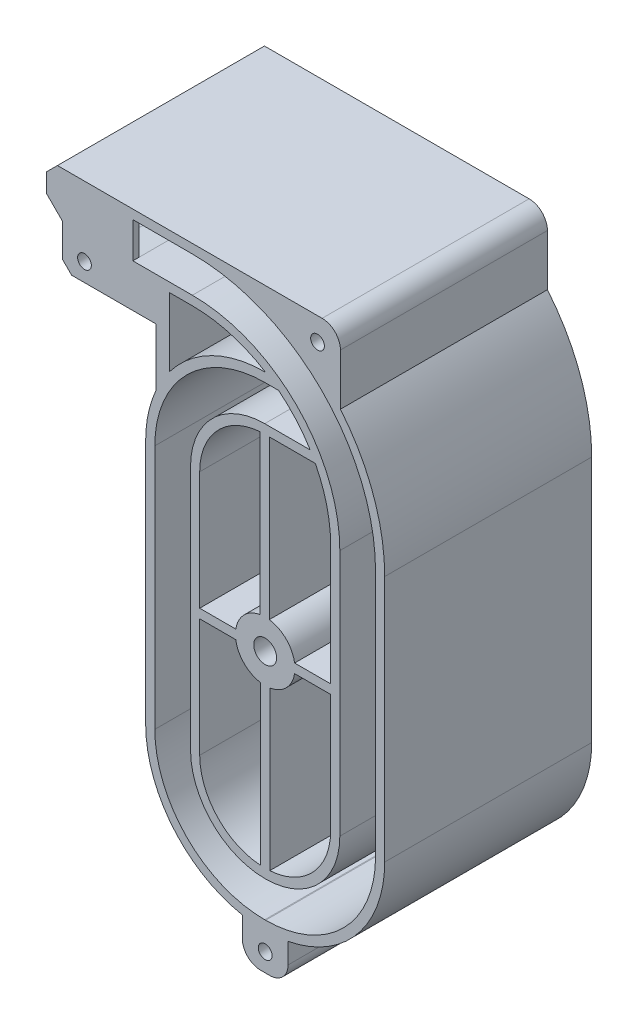
SolidWorks part; units mm, degrees
ref_plane "Front Plane" through (0, 0, 0) normal (0, 0, 1) x (1, 0, 0)
ref_plane "Top Plane" through (0, 0, 0) normal (0, 1, 0) x (1, 0, 0)
ref_plane "Right Plane" through (0, 0, 0) normal (1, 0, 0) x (0, 0, -1)
sketch "Sketch5" plane through (0, 0, 0) normal (0, 0, 1) x (1, 0, 0)
  line L5 (0, 0) -> (0, 6) construction
  line L6 (4.8529, 0) -> (10.55, 5.6971)
  line L11 (6.55, 0) -> (10.55, 4)
  line L18 (-2.55, 6) -> (-6.55, 2)
  line L19 (-6.55, 2) -> (-6.55, 0)
  line L20 (7.0145, 15.5645) -> (16.104, 18) construction
  line L23 (6.55, 0) -> (-6.55, 0)
  line L24 (-5.35, 1.5029) -> (-0.8529, 6)
  line L25 (-5.35, 1.5029) -> (-5.35, 0)
  line L26 (-2.55, 6) -> (-0.8529, 6) construction
  line L27 (-2.55, 6) -> (7.0145, 15.5645)
  line L28 (-0.8529, 6) -> (7.0145, 13.8674)
  line L29 (16.104, 16) -> (6.6006, 13.4536)
  line L31 (7.0145, 11.55) -> (7.0145, 15.5645)
  line L32 (16.104, 7) -> (16.104, 5.8) construction
  line L33 (16.104, 5.8) -> (16.104, 5) construction
  line L34 (7.0145, 13.8674) -> (6.6006, 13.4536)
  line L35 (10.55, 5.6971) -> (16.104, 7)
  line L36 (16.104, 7) -> (19.104, 7)
  line L38 (10.55, 4) -> (16.104, 5)
  line L41 (69.1095, -24) -> (69.1095, -78)
  line L42 (78.9095, -24) -> (78.9095, -78)
  line L44 (80.9095, -78) -> (80.9095, -24)
  line L46 (16.104, 16) -> (16.104, 18) construction
  line L49 (30.7095, -78) -> (30.7095, -24.3867)
  line L50 (71.1095, -24) -> (71.1095, -78)
  line L51 (19.104, 7) -> (19.104, 5.8) construction
  line L62 (16.104, 5) -> (19.104, 5)
  line L63 (19.104, 5) -> (19.104, 5.8) construction
  line L64 (19.104, 7) -> (25.9095, 8.2)
  line L73 (19.104, 5) -> (25.9095, 6.2)
  line L74 (16.104, 5.8) -> (19.104, 5.8) construction
  line L93 (63.9212, 18) -> (16.104, 18) construction
  line L94 (16.104, 16) -> (38.9095, 16)
  line L95 (6.8145, 15.3645) -> (6.8145, 11.4672) construction
  line L96 (25.9095, 8.2) -> (38.9095, 8.2)
  line L97 (7.0145, 15.5645) -> (9.45, 18)
  line L104 (6.8145, 11.4672) -> (10.35, 7.9316) construction
  line L105 (-6.55, 0) -> (-6.55, -1.2)
  line L106 (-6.55, -1.2) -> (6.55, -1.2)
  line L107 (6.55, -1.2) -> (6.55, 0)
  line L108 (-5.35, 0) -> (-5.35, -1.2)
  line L109 (4.8529, 0) -> (4.8529, -1.2)
  line L111 (10.55, 8.0145) -> (7.0145, 11.55)
  line L113 (10.35, 7.9316) -> (10.35, 3.8) construction
  line L114 (10.55, 4) -> (10.55, 8.0145)
  line L133 (9.45, 18) -> (38.9095, 18)
  line L134 (25.9095, 6.2) -> (38.9095, 6.2)
  line L135 (54.9095, -78) -> (80.9095, -78) construction
  line L137 (54.9095, -78) -> (54.9095, -104) construction
  line L138 (54.7095, -78) -> (54.7095, -104) construction
  line L139 (54.7095, -78) -> (28.7095, -78) construction
  line L140 (54.9095, -104) -> (54.7095, -104)
  line L141 (54.9095, -102) -> (54.7095, -102)
  line L142 (54.9095, -94.2) -> (54.7095, -94.2)
  line L143 (54.9095, -92.2) -> (54.7095, -92.2)
  line L146 (28.7095, -24.3867) -> (28.7095, -78)
  line L147 (40.5095, -24.3867) -> (40.5095, -78)
  line L148 (38.5095, -24.3867) -> (38.5095, -78)
  line L151 (54.7095, -24.3867) -> (28.7095, -24.3867) construction
  line L152 (54.7095, -24.3867) -> (54.7095, 1.6133) construction
  line L153 (54.7095, -24.3867) -> (69.1095, -24.3867) construction
  line L154 (54.7095, 1.6133) -> (54.9095, 1.6133)
  line L155 (54.7095, -0.3867) -> (57.7365, -0.3867)
  line L156 (54.7095, -8.1867) -> (66.9591, -8.1867)
  line L157 (54.7095, -10.1867) -> (67.9962, -10.1867)
  line L158 (69.1095, -51.1934) -> (40.5095, -51.1934) construction
  line L161 (48.3869, -50.1934) -> (40.5095, -50.1934)
  line L162 (61.2322, -50.1934) -> (69.1095, -50.1934)
  line L163 (48.3869, -52.1934) -> (40.5095, -52.1934)
  line L164 (61.2322, -52.1934) -> (69.1095, -52.1934)
  line L165 (30.9625, -13.8) -> (30.9625, 6.2)
  line L166 (33.9625, -8.7163) -> (33.9625, 6.2)
  line L167 (53.7095, -10.222) -> (53.7095, -44.7871)
  line L168 (68.1095, -78) -> (69.1095, -77)
  line L169 (54.9095, -91.2) -> (53.9095, -92.2)
  line L170 (55.7095, -10.222) -> (55.7095, -44.7871)
  line L171 (55.7095, -10.222) -> (55.7095, -10.1867)
  line L172 (53.8095, -57.616) -> (53.8095, -92.1715)
  line L173 (55.8095, -57.616) -> (55.8095, -92.1715)
  line L174 (7.0145, 14.1645) -> (16.104, 16)
  line L175 (10.55, 5.0971) -> (16.104, 7)
  line L176 (7.0145, 14.1645) -> (7.0145, 13.5645)
  arc A2 (80.9095, -24) -> (38.9095, 18) centre (38.9095, -24) ccw
  arc A9 (78.9095, -24) -> (38.9095, 16) centre (38.9095, -24) ccw
  arc A10 (71.1095, -24) -> (38.9095, 8.2) centre (38.9095, -24) ccw
  arc A11 (69.1095, -24) -> (38.9095, 6.2) centre (38.9095, -24) ccw
  arc A12 (54.9095, -102) -> (78.9095, -78) centre (54.9095, -78) ccw
  arc A13 (54.9095, -104) -> (80.9095, -78) centre (54.9095, -78) ccw
  arc A14 (54.9095, -94.2) -> (71.1095, -78) centre (54.9095, -78) ccw
  arc A15 (54.9095, -92.2) -> (69.1095, -78) centre (54.9095, -78) ccw
  arc A16 (28.7095, -78) -> (54.7095, -104) centre (54.7095, -78) ccw
  arc A17 (30.7095, -78) -> (54.7095, -102) centre (54.7095, -78) ccw
  arc A18 (38.5095, -78) -> (54.7095, -94.2) centre (54.7095, -78) ccw
  arc A19 (40.5095, -78) -> (54.7095, -92.2) centre (54.7095, -78) ccw
  arc A39 (54.7095, 1.6133) -> (28.7095, -24.3867) centre (54.7095, -24.3867) ccw
  arc A40 (54.7095, -0.3867) -> (30.7095, -24.3867) centre (54.7095, -24.3867) ccw
  arc A41 (54.7095, -8.1867) -> (38.5095, -24.3867) centre (54.7095, -24.3867) ccw
  arc A42 (54.7095, -10.1867) -> (40.5095, -24.3867) centre (54.7095, -24.3867) ccw
  circle A43 centre (54.8095, -51.1934) radius 6.5
  circle A44 centre (54.8095, -51.1934) radius 2.5
  arc A49 (54.9095, -91.2) -> (68.1095, -78) centre (54.9095, -78) ccw
  point P20 (0, 0)
  point P107 (54.8095, -51.1934)
  point P110 (40.5095, -51.1934)
  dimension "D16" = 2
  dimension "D17" = 2
  dimension "D10" = 0.2
  dimension "D12" = 2
  dimension "D13" = 0.8
  dimension "D14" = 2
  dimension "D15" = 40
  dimension "D11" = 0.2
  dimension "D22" = 2
  dimension "D28" = 18
  dimension "D33" = 5
  dimension "D18" = 24
  dimension "D21" = 24
  dimension "D23" = 0.2
  dimension "D24" = 2
  dimension "D34" = 24
  dimension "D35" = 4
  dimension "D36" = 2
  dimension "D37" = 3
  dimension "D38" = 1
  dimension "D39" = 45
  dimension "D40" = 45
  dimension "D43" = 0.2
  dimension "D46" = 0.9
  dimension "D47" = 0.9
  dimension "D44" = 2
  dimension "D1" = 6
  dimension "D2" = 135
  dimension "D3" = 13.1
  dimension "D4" = 2
  dimension "D5" = 1.2
  dimension "D6" = 1.2
  dimension "D7" = 1.2
  dimension "D8" = 10.2029
  dimension "D9" = 1.2
  dimension "D19" = 3
  dimension "D20" = 120
  dimension "D25" = 0.2
  dimension "D26" = 135
  dimension "D27" = 5
  dimension "D29" = 2
  dimension "D30" = 9
  dimension "D31" = 150
  dimension "D32" = 5
  dimension "D41" = 10
  dimension "D42" = 7.8
  dimension "D45" = 20
  dimension "D48" = 0.6
  dimension "D49" = 0.6
  dimension "D84" = 13
sketch "Sketch9" plane through (0, 0, 0) normal (0, 0, 1) x (1, 0, 0)
  line L4 (16.104, 5) -> (19.104, 5)
  line L5 (15.35, 2.8) -> (15.35, 4.9213) construction
  line L6 (15.35, 4.9213) -> (14.2893, 3.8607) construction
  line L7 (15.35, 4.9213) -> (16.4107, 3.8607) construction
  line L8 (6.8145, -1.2) -> (6.8145, 18)
  line L9 (6.8145, 18) -> (71.2408, 18)
  line L10 (71.2408, 18) -> (71.2408, 8)
  line L11 (71.2408, 8) -> (6.8145, 8) construction
  line L12 (63.8642, 9.7826) -> (66.2408, 13) construction
  line L13 (30.9625, -1.2) -> (30.9625, 6.2)
  line L14 (30.9625, -13.8) -> (30.9625, 6.2) construction
  line L15 (54.8095, -104) -> (54.8095, -112) construction
  line L16 (115.873, 7.0843) -> (115.873, 9.2056) construction
  line L17 (6.8145, -1.2) -> (71.2408, -1.2)
  line L18 (71.2408, -1.2) -> (71.2408, 8)
  line L20 (21.35, 5.396) -> (21.35, -1.2)
  line L21 (9.45, 18) -> (38.9095, 18) construction
  line L22 (19.35, -1.2) -> (19.35, 18)
  line L25 (19.104, 5) -> (19.35, 5.0434)
  line L26 (16.104, 7) -> (19.104, 7)
  line L27 (115.873, 9.2056) -> (114.8123, 8.1449) construction
  line L28 (115.873, 9.2056) -> (116.9336, 8.1449) construction
  line L30 (7.0145, 11.55) -> (7.0145, 13.8674)
  line L31 (10.35, 7.9316) -> (6.8145, 11.4672) construction
  line L32 (6.8145, 11.4672) -> (10.35, 7.9316) construction
  line L34 (10.35, 7.9316) -> (10.35, 3.8) construction
  line L35 (10.55, 5.0971) -> (16.104, 7)
  line L36 (19.104, 7) -> (19.35, 7.0434)
  line L37 (19.104, 7) -> (25.9095, 8.2) construction
  line L38 (-6.55, -1.2) -> (6.55, -1.2) construction
  line L39 (19.104, 5) -> (25.9095, 6.2) construction
  line L40 (19.35, 5.0434) -> (25.9095, 6.2)
  line L41 (25.9095, 6.2) -> (30.9625, 6.2)
  line L42 (19.35, 7.0434) -> (25.9095, 8.2)
  line L43 (10.55, 4) -> (10.55, -1.2)
  line L44 (7.0145, 11.55) -> (10.55, 8.0145)
  line L45 (10.55, 8.0145) -> (10.55, 4)
  line L46 (25.9095, 8.2) -> (25.9095, 6.2)
  line L47 (7.0145, 13.8674) -> (6.6006, 13.4536)
  line L48 (6.6006, 13.4536) -> (16.104, 16)
  line L49 (16.104, 16) -> (19.35, 16)
  line L50 (16.104, 16) -> (38.9095, 16) construction
  line L51 (10.55, 5.6971) -> (16.104, 7)
  line L52 (25.9095, 8.2) -> (25.9095, 18)
  line L53 (49.8095, -112) -> (59.8095, -112)
  line L54 (10.55, 4) -> (16.104, 5)
  line L55 (19.35, 16) -> (25.9095, 16)
  line L56 (6.8145, 15.3645) -> (6.8145, 11.4672) construction
  line L57 (9.45, 18) -> (6.8145, 15.3645)
  line L58 (7.0145, 13.8674) -> (6.8145, 13.6674)
  line L59 (-0.8529, 6) -> (7.0145, 13.8674) construction
  line L60 (7.0145, 15.5645) -> (7.0145, 18)
  line L61 (7.0145, 15.5645) -> (7.0145, 13.8674)
  line L62 (63.8642, 9.7826) -> (38.9095, -24) construction
  line L63 (49.8095, -112) -> (49.8095, -103.5341)
  line L64 (59.8095, -112) -> (59.8095, -103.5341)
  line L65 (54.9095, -104) -> (54.7095, -104) construction
  line L66 (54.7095, -104) -> (54.9095, -104)
  line L67 (19.35, -1.2) -> (19.35, -4.4)
  line L68 (19.35, -4.4) -> (30.9625, -4.4)
  line L69 (30.9625, -4.4) -> (30.9625, -1.2)
  line L70 (7.0145, 14.1645) -> (16.104, 16)
  arc A4 (7.0145, 13.0671) -> (6.8145, 12.7624) centre (58.8917, -21.2) ccw
  circle A7 centre (66.2408, 13) radius 1.5
  arc A9 (28.7095, -78) -> (54.7095, -104) centre (54.7095, -78) ccw construction
  circle A12 centre (115.873, 7.0843) radius 1.5 construction
  circle A13 centre (15.35, 2.8) radius 1.5
  arc A14 (80.9095, -24) -> (38.9095, 18) centre (38.9095, -24) ccw construction
  arc A15 (54.9095, -104) -> (80.9095, -78) centre (54.9095, -78) ccw construction
  arc A20 (71.2408, 2.8083) -> (38.9095, 18) centre (38.9095, -24) ccw
  arc A21 (71.2408, 2.8083) -> (38.9095, 18) centre (38.9095, -24) ccw
  arc A22 (54.9095, -104) -> (59.8095, -103.5341) centre (54.9095, -78) ccw
  arc A23 (54.7095, -104) -> (49.8095, -103.5341) centre (54.7095, -78) cw
  circle A24 centre (54.8095, -108) radius 1.5
  point P103 (54.8095, -112)
  dimension "D1" = 5
  dimension "D2" = 5
  dimension "D8" = 2
  dimension "D9" = 3
  dimension "D10" = 4
  dimension "D6" = 135
  dimension "D13" = 4
  dimension "D7" = 5
  dimension "D5" = 3
  dimension "D11" = 0
  dimension "D12" = 3.2
  dimension "D14" = 8
  dimension "D4" = 4
  dimension "D15" = 3
  dimension "D3" = 5
  dimension "D16" = 5
extrude "Boss-Extrude6" add sketch "Sketch9" along normal blind 22.6 and the other way blind 22.6 contours L45 L51 L26 L36 L22 L49 L48 L47 L30 L44 | L55 L22 L42 L52 | L46 L42 L22 L40 | L45 L54 L4 L25 L22 L36 L26 L51 | L54 L43 L17 L22 L25 L4 A13 | L40 L22 L17 L20 | L22 L55 L52 L9 | L57 L61 L47 L48 L49 L22 L9 | L41 L40 L20 L17 L13 | L70 L61 L30 L48 | L51 L45 L35 region at (15.3734, 5.6273, 0) region at (17.604, 4.8921, 0) region at (20.3592, 2.0107, 0) region at (22.6298, 6.6217, 0) region at (12.4013, 5.9314, 0) region at (14.0234, 11.1808, 0) region at (22.5543, 11.8042, 0) region at (26.2432, 2.4092, 0) region at (12.8397, 16.5339, 0) region at (22.6298, 17, 0) region at (10.0443, 14.5763, 0)
extrude "Boss-Extrude7" add sketch "Sketch5" along normal up to surface and the other way up to surface contours A39 L166 A11 L134 L165 | A40 L155 A11 L154 A39 L146 A16 L140 A13 L44 A2 L133 L97 L31 L34 L29 L94 A9 L42 A12 L141 A17 L49 | A42 L157 L156 A41 L148 A18 L142 A14 L50 A10 L96 L64 L36 L35 L114 L38 L62 L73 L134 A11 L41 A15 L143 A19 L147 | A43 A44 | A43 L164 L41 L162 | A43 L161 L147 L163 | A11 L156 A10 L96 L64 L36 L35 L114 L38 L62 L73 L134 | A11 L157 A10 L156 | A43 L170 L171 L157 A42 L167 | L169 A49 L173 A43 L172 A19 | A49 L169 A19 L143 A15 L173 region at (17.604, 6.4126, 0) region at (11.2769, 16.4804, 0) region at (66.352, -9.1802, 0) region at (32.3895, -2.4803, 0) region at (64.4195, -9.6275, 0) region at (54.7095, -27.4562, 0) region at (65.1966, -51.1934, 0) region at (59.2409, -46.6926, 0) region at (44.4224, -51.1934, 0) region at (54.8039, -74.5827, 0) region at (55.084, -91.7513, 0) up to face at (17.5914, 9.0143, 22.6) other way up to face at (17.5914, 9.0143, -22.6)
extrude "Cut-Extrude1" cut sketch "Sketch9<30>" against normal blind 21.2 and the other way blind 21.2 contours L45 L51 L26 L36 L22 L49 L48 L47 L30 L44 | L55 L22 L42 L52 | L4 A13 L54 L43 L17 L22 L25 | A13 | L51 L45 L35 | L70 L61 L30 L48 region at (17.604, 4.8921, 0) region at (12.4013, 5.9314, 0) region at (14.0234, 11.1808, 0) region at (22.5543, 11.8042, 0) region at (10.0443, 14.5763, 0) region at (15.35, 2.8, 0)
sketch "Sketch9<30>" plane through (0, 0, 0) normal (0, 0, 1) x (1, 0, 0) same geometry as "Sketch9"
extrude "Boss-Extrude8" add sketch "Sketch9<31>" along normal blind 22.6 and the other way blind 22.6 contours A20 L18 L10 L9 A7 | L66 A23 L63 L53 L64 A22 A24 region at (63.3426, 13.6608, 0) region at (49.9406, -107.767, 0)
sketch "Sketch9<31>" plane through (0, 0, 0) normal (0, 0, 1) x (1, 0, 0) same geometry as "Sketch9"
fillet "Fillet1" radius 4 3 edges at (71.2408, 18, 0) (49.8095, -112, 0) (59.8095, -112, 0)
chamfer "Chamfer1" distance 2 angle 45 2 edges at (10.55, -1.2, 21.9) (10.55, -1.2, -21.9)
chamfer "Chamfer2" distance 10 angle 45 2 edges at (19.35, 1.9217, -21.2) (19.35, 1.9217, 21.2)
sketch "Sketch11" plane through (0, -1.2, 0) normal (0, -1, 0) x (1, 0, 0)
  line L0 (9.45, 0) -> (38.9095, 0) construction
  line L2 (23.35, -10) -> (23.35, 10) construction
  line L3 (19.35, 11.2) -> (19.35, -11.2) construction
  circle A0 centre (23.35, 10) radius 2.5
  circle A1 centre (23.35, -10) radius 2.5
  point P8 (23.35, 0)
  dimension "D1" = 5
  dimension "D3" = 4
  dimension "D2" = 20
extrude "Cut-Extrude5" cut sketch "Sketch11" against normal blind 4
